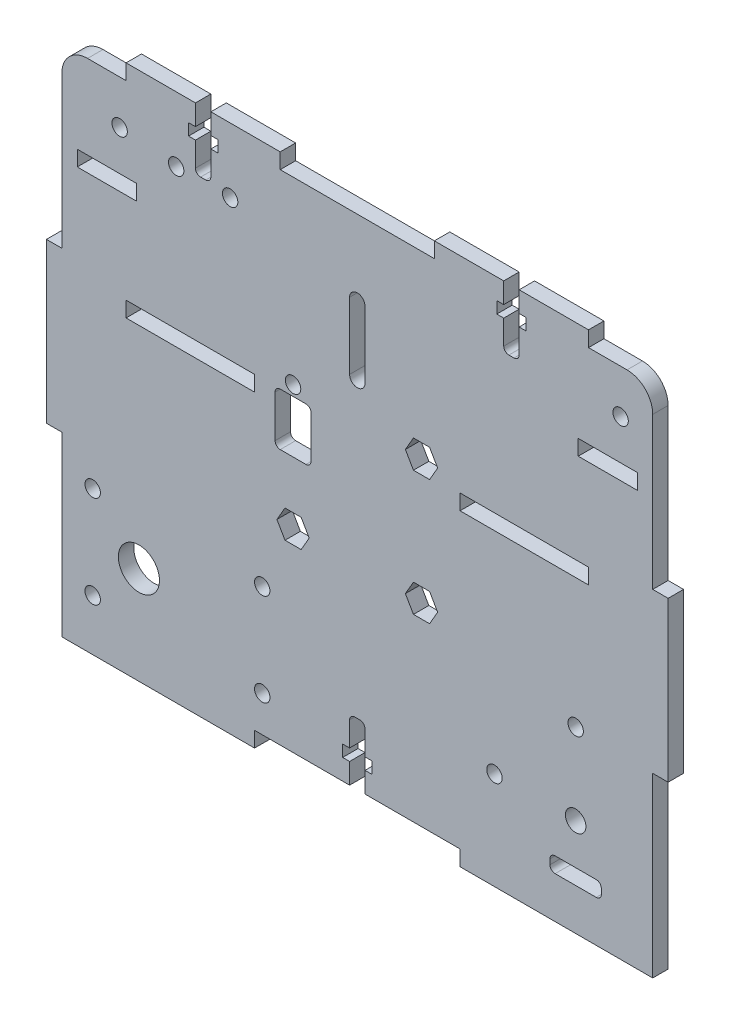
SolidWorks part; units mm, degrees
other "Marcação1"
sketch "Esboço7" plane through (-68, 31.5, 3) normal (-0.6758, 0.2828, 0.6807) x (0.7271, 0.1043, 0.6785)
sketch "Esboço8" plane through (-68, 31.5, 3) normal (-0.6758, 0.2828, 0.6807) x (0.7271, 0.1043, 0.6785)
sketch "Esboço9" plane through (-68, 31.5, 3) normal (-0.6758, 0.2828, 0.6807) x (0.7271, 0.1043, 0.6785)
sketch "Esboço10" plane through (-68, 31.5, 3) normal (-0.6758, 0.2828, 0.6807) x (0.7271, 0.1043, 0.6785)
sketch "Esboço11" plane through (-68, 36.25, 3) normal (-0.6758, 0.2828, 0.6807) x (0.7271, 0.1043, 0.6785)
sketch "Esboço13" plane through (-68, 36.25, 3) normal (-0.6758, 0.2828, 0.6807) x (0.7271, 0.1043, 0.6785)
sketch "Esboço15" plane through (-68, 36.25, 3) normal (-0.6758, 0.2828, 0.6807) x (0.7271, 0.1043, 0.6785)
sketch "Esboço19" plane through (-68, 66.25, 3) normal (-0.6758, 0.2828, 0.6807) x (0.7271, 0.1043, 0.6785)
sketch "Esboço22" plane through (-68, 95.5577, 3) normal (-0.6758, 0.2828, 0.6807) x (0.7271, 0.1043, 0.6785)
sketch "Sketch16" plane through (-60.5, 53, 1.5) normal (-0.6758, 0.2828, 0.6807) x (0.7271, 0.1043, 0.6785)
sketch "Sketch18" plane through (-60.5, 53, 1.5) normal (-0.6758, 0.2828, 0.6807) x (0.7271, 0.1043, 0.6785)
material "Acrylic (Medium-high impact)"
ref_plane "Plano frontal" through (0, 0, 0) normal (0, 0, 1) x (1, 0, 0)
ref_plane "Plano superior" through (0, 0, 0) normal (0, 1, 0) x (1, 0, 0)
ref_plane "Plano direito" through (0, 0, 0) normal (1, 0, 0) x (0, 0, -1)
sketch "Esboço1" plane through (0, 0, 0) normal (0, 0, 1) x (1, 0, 0)
  line L6 (57.5, -50) -> (-57.5, -50)
  line L8 (57.5, -50) -> (57.5, 50)
  line L9 (57.5, 50) -> (-57.5, 50)
  line L10 (-57.5, -50) -> (-57.5, 50)
  line L11 (57.5, -50) -> (-57.5, 50) construction
  line L12 (57.5, 50) -> (-57.5, -50) construction
  point P0 (0, 0)
  dimension "D1" = 100
  dimension "D2" = 115
extrude "Ressalto-extrusão1" add sketch "Esboço1" along normal mid plane 3
sketch "Esboço2" plane through (0, 0, 1.5) normal (0, 0, 1) x (1, 0, 0)
  line L1 (-20, -50) -> (20, -50)
  line L2 (-20, -50) -> (-20, -47)
  line L3 (-20, -47) -> (20, -47)
  line L4 (20, -50) -> (20, -47)
  line L6 (-57.5, -50) -> (57.5, -50) construction
  line L15 (57.5, 50) -> (-57.5, 50) construction
  line L25 (-45, 13) -> (-20, 13)
  line L26 (-45, 13) -> (-45, 10)
  line L29 (-45, 10) -> (-20, 10)
  line L30 (-20, 13) -> (-20, 10)
  line L31 (0, -1.65) -> (0, 1.65) construction
  line L32 (20, 13) -> (20, 10)
  line L33 (45, 10) -> (20, 10)
  line L34 (45, 13) -> (45, 10)
  line L35 (45, 13) -> (20, 13)
  point P6 (0, -47)
  dimension "D4" = 25
  dimension "D3" = 3
  dimension "D1" = 37
  dimension "D2" = 40
  dimension "D5" = 40
extrude "Corte-extrusão1" cut sketch "Esboço2" against normal through all
sketch "Sketch9" plane through (0, 0, 0) normal (0, 0, 1) x (1, 0, 0)
  line L0 (20, -47) -> (-20, -47) construction
  line L1 (-1.5, -47) -> (1.5, -47)
  line L2 (-1.5, -47) -> (-1.5, -43)
  line L3 (-0.5, -35) -> (0.5, -35)
  line L4 (1.5, -47) -> (1.5, -43)
  line L5 (1.5, -40.73) -> (2.85, -40.73)
  line L6 (-2.85, -40.73) -> (-1.5, -40.73)
  line L7 (-2.85, -40.73) -> (-2.85, -43)
  line L8 (-2.85, -43) -> (-1.5, -43)
  line L9 (2.85, -40.73) -> (2.85, -43)
  line L10 (-1.5, -40.73) -> (-1.5, -36)
  line L11 (1.5, -43) -> (2.85, -43)
  line L12 (1.5, -40.73) -> (1.5, -36)
  arc A0 (0.5, -35) -> (1.5, -36) centre (0.5, -36) cw
  arc A1 (-1.5, -36) -> (-0.5, -35) centre (-0.5, -36) cw
  point P6 (0, -35)
  point P18 (1.5, -35)
  point P21 (-1.5, -35)
  dimension "D7" = 1
  dimension "D1" = 3
  dimension "D2" = 12
  dimension "D3" = 2.27
  dimension "D4" = 1.35
  dimension "D5" = 1.35
  dimension "D6" = 4
extrude "Cut-Extrude12" cut sketch "Sketch9" against normal through all both and the other way through all
sketch "Esboço3" plane through (0, 0, 1.5) normal (0, 0, 1) x (1, 0, 0)
  line L0 (57.5, -50) -> (57.5, 50) construction
  line L1 (57.5, 15.5) -> (60.5, 15.5)
  line L2 (57.5, 15.5) -> (57.5, -15.5)
  line L3 (57.5, -15.5) -> (60.5, -15.5)
  line L4 (60.5, 15.5) -> (60.5, -15.5)
  line L5 (0, -1.65) -> (0, 1.65) construction
  line L6 (-57.5, -15.5) -> (-60.5, -15.5)
  line L7 (-57.5, 15.5) -> (-60.5, 15.5)
  line L8 (-57.5, 15.5) -> (-57.5, -15.5)
  line L9 (-60.5, 15.5) -> (-60.5, -15.5)
  line L15 (57.5, 50) -> (-57.5, 50) construction
  line L16 (-45, 50) -> (-15, 50)
  line L17 (-45, 50) -> (-45, 53)
  line L18 (-45, 53) -> (-15, 53)
  line L19 (-15, 50) -> (-15, 53)
  line L20 (15, 50) -> (15, 53)
  line L21 (45, 53) -> (15, 53)
  line L22 (45, 50) -> (45, 53)
  line L23 (45, 50) -> (15, 50)
  line L24 (-57.5, 50) -> (-57.5, -50) construction
  point P6 (57.5, 0)
  dimension "D1" = 3
  dimension "D2" = 31
  dimension "D3" = 30
  dimension "D4" = 15
  dimension "D5" = 12.5
extrude "Ressalto-extrusão2" add sketch "Esboço3" against normal through all
sketch "Esboço30" plane through (0, 0, -1.5) normal (0, 0, -1) x (-1, 0, 0)
  line L2 (57.5, -15.5) -> (57.5, -50) construction
  line L6 (57.5, -50) -> (20, -50) construction
  circle A1 centre (42.5, -31) radius 4
  dimension "D1" = 15
  dimension "D2" = 19
  dimension "D3" = 8
extrude "Corte-extrusão11" cut sketch "Esboço30" against normal through all both and the other way through all
sketch "Esboço4" plane through (0, 0, 1.5) normal (0, 0, 1) x (1, 0, 0)
  line L0 (57.5, -50) -> (57.5, -15.5) construction
  line L76 (-46.5, -31) -> (-38.5, -31) construction
  circle A11 centre (42.5, -31) radius 2
  circle A14 centre (-42.5, -31) radius 4 construction
  dimension "D1" = 15
  dimension "D2" = 4
extrude "Corte-extrusão2" cut sketch "Esboço4" against normal through all
sketch "Esboço31" plane through (0, 0, -1.5) normal (0, 0, -1) x (-1, 0, 0)
  line L1 (57.5, -15.5) -> (57.5, -50) construction
  line L2 (46.5, -31) -> (38.5, -31) construction
  circle A4 centre (51.5, -22) radius 1.5
  circle A5 centre (51.5, -40) radius 1.5
  circle A6 centre (42.5, -31) radius 4 construction
  circle A7 centre (18.5, -22) radius 1.5
  circle A8 centre (18.5, -40) radius 1.5
  dimension "D1" = 3
  dimension "D3" = 6
  dimension "D4" = 18
  dimension "D5" = 33
extrude "Corte-extrusão12" cut sketch "Esboço31" against normal through all both and the other way through all
sketch "Sketch8" [suppressed] plane through (0, 0, -1.5) normal (0, 0, -1) x (-1, 0, 0)
  line L31 (-57.5, 39.6519) -> (-53.4896, 39.6519)
  line L32 (-58, 31.6519) -> (-58, 23.6519) construction
  line L33 (-57.5, 23.6519) -> (-53.4896, 23.6519)
  line L34 (-45, 36.6519) -> (-45, 26.6519)
  line L35 (-57.5, 15.5) -> (-57.5, 50) construction
  line L37 (-48.5, 41.4019) -> (-50, 44)
  line L38 (-50, 44) -> (-53, 44)
  line L39 (-53, 44) -> (-54.5, 41.4019)
  line L40 (-54.5, 41.4019) -> (-53.4896, 39.6519)
  line L42 (-49.5104, 39.6519) -> (-48.5, 41.4019)
  line L43 (-49.5104, 39.6519) -> (-48, 39.6519)
  line L45 (-51.7693, 38.8038) -> (-50.2755, 38.8038) [skipped]
  line L46 (-58, 31.6519) -> (-45, 31.6519) construction
  line L48 (-49.5104, 23.6519) -> (-48.5, 21.9019)
  line L49 (-54.5, 21.9019) -> (-53.4896, 23.6519)
  line L50 (-53, 19.3038) -> (-54.5, 21.9019)
  line L51 (-50, 19.3038) -> (-53, 19.3038)
  line L52 (-48.5, 21.9019) -> (-50, 19.3038)
  line L53 (-49.5104, 23.6519) -> (-48, 23.6519)
  line L54 (-57.5, 23.6519) -> (-57.5, 39.6519)
  line L55 (-58, 39.6519) -> (-57.5, 39.6519) construction
  line L56 (-58, 39.6519) -> (-58, 31.6519) construction
  line L57 (-58, 23.6519) -> (-57.5, 23.6519) construction
  line L58 (-57.5, 50) -> (-45, 50) construction
  line L59 (0, 1.65) -> (0, -1.65) construction
  line L60 (58, 23.6519) -> (57.5, 23.6519) construction
  line L61 (58, 39.6519) -> (58, 31.6519) construction
  line L62 (58, 39.6519) -> (57.5, 39.6519) construction
  line L63 (58, 31.6519) -> (45, 31.6519) construction
  line L64 (58, 31.6519) -> (58, 23.6519) construction
  line L65 (57.5, 23.6519) -> (57.5, 39.6519)
  line L66 (49.5104, 23.6519) -> (48, 23.6519)
  line L67 (48.5, 21.9019) -> (50, 19.3038)
  line L68 (50, 19.3038) -> (53, 19.3038)
  line L69 (53, 19.3038) -> (54.5, 21.9019)
  line L70 (54.5, 21.9019) -> (53.4896, 23.6519)
  line L71 (49.5104, 23.6519) -> (48.5, 21.9019)
  line L72 (49.5104, 39.6519) -> (48, 39.6519)
  line L73 (49.5104, 39.6519) -> (48.5, 41.4019)
  line L74 (54.5, 41.4019) -> (53.4896, 39.6519)
  line L75 (53, 44) -> (54.5, 41.4019)
  line L76 (50, 44) -> (53, 44)
  line L77 (48.5, 41.4019) -> (50, 44)
  line L78 (45, 36.6519) -> (45, 26.6519)
  line L79 (57.5, 23.6519) -> (53.4896, 23.6519)
  line L80 (57.5, 39.6519) -> (53.4896, 39.6519)
  arc A10 (-48, 23.6519) -> (-45, 26.6519) centre (-48, 26.6519) ccw
  arc A12 (-48, 39.6519) -> (-45, 36.6519) centre (-48, 36.6519) cw
  arc A14 (-49.25, 40.1029) -> (-53.75, 40.1029) centre (-51.5, 41.4019) ccw construction
  arc A15 (-49.25, 23.201) -> (-53.75, 23.201) centre (-51.5, 21.9019) cw construction
  arc A16 (49.25, 23.201) -> (53.75, 23.201) centre (51.5, 21.9019) ccw construction
  arc A17 (49.25, 40.1029) -> (53.75, 40.1029) centre (51.5, 41.4019) cw construction
  arc A18 (48, 39.6519) -> (45, 36.6519) centre (48, 36.6519) ccw
  arc A19 (48, 23.6519) -> (45, 26.6519) centre (48, 26.6519) cw
  point P9 (-45, 23.6519)
  point P14 (-45, 39.6519)
  point P17 (-58, 39.6519)
  point P38 (-51.5, 31.6519)
  point P73 (45, 39.6519)
  point P74 (45, 23.6519)
  dimension "D1" = 13
  dimension "D2" = 3
  dimension "D5" = 3
  dimension "D6" = 3
  dimension "D3" = 16
  dimension "D7" = 19.5
  dimension "D8" = 6
sketch "Sketch11" plane through (0, 0, 0) normal (0, 0, 1) x (1, 0, 0)
  line L0 (45, 53) -> (15, 53) construction
  line L1 (28.5, 53) -> (31.5, 53)
  line L2 (28.5, 53) -> (28.5, 49)
  line L3 (29.5, 41) -> (30.5, 41)
  line L4 (31.5, 53) -> (31.5, 49)
  line L5 (15, 53) -> (15, 50) construction
  line L6 (28.5, 46.73) -> (28.5, 42)
  line L7 (27.15, 49) -> (28.5, 49)
  line L8 (27.15, 49) -> (27.15, 46.73)
  line L9 (27.15, 46.73) -> (28.5, 46.73)
  line L10 (32.85, 49) -> (32.85, 46.73)
  line L11 (31.5, 49) -> (32.85, 49)
  line L12 (31.5, 46.73) -> (31.5, 42)
  line L13 (31.5, 46.73) -> (32.85, 46.73)
  line L27 (0, -1.65) -> (0, 1.65) construction
  line L28 (-31.5, 46.73) -> (-32.85, 46.73)
  line L29 (-31.5, 46.73) -> (-31.5, 42)
  line L30 (-31.5, 49) -> (-32.85, 49)
  line L31 (-32.85, 49) -> (-32.85, 46.73)
  line L32 (-27.15, 46.73) -> (-28.5, 46.73)
  line L33 (-27.15, 49) -> (-27.15, 46.73)
  line L34 (-27.15, 49) -> (-28.5, 49)
  line L35 (-28.5, 46.73) -> (-28.5, 42)
  line L36 (-31.5, 53) -> (-31.5, 49)
  line L37 (-29.5, 41) -> (-30.5, 41)
  line L38 (-28.5, 53) -> (-28.5, 49)
  line L39 (-28.5, 53) -> (-31.5, 53)
  arc A0 (30.5, 41) -> (31.5, 42) centre (30.5, 42) ccw
  arc A1 (28.5, 42) -> (29.5, 41) centre (29.5, 42) ccw
  arc A4 (-28.5, 42) -> (-29.5, 41) centre (-29.5, 42) cw
  arc A5 (-30.5, 41) -> (-31.5, 42) centre (-30.5, 42) cw
  point P20 (28.5, 41)
  point P39 (-28.5, 41)
  dimension "D8" = 1
  dimension "D1" = 3
  dimension "D2" = 12
  dimension "D3" = 13.5
  dimension "D4" = 1.35
  dimension "D5" = 2.27
  dimension "D6" = 1.35
  dimension "D7" = 4
extrude "Cut-Extrude14" cut sketch "Sketch11" against normal through all both and the other way through all
sketch "Sketch13" plane through (0, 0, 0) normal (0, 0, 1) x (1, 0, 0)
  line L18 (-10, 13.0193) -> (-15, 13.0193)
  line L19 (-9, 12.0193) -> (-9, 3.8193)
  line L20 (-10, 2.8193) -> (-15, 2.8193)
  line L21 (-16, 12.0193) -> (-16, 3.8193)
  line L23 (15.64, 15.0193) -> (14.07, 17.7386)
  line L24 (14.07, 17.7386) -> (10.93, 17.7386)
  line L25 (10.93, 17.7386) -> (9.36, 15.0193)
  line L26 (9.36, 15.0193) -> (10.93, 12.3)
  line L27 (10.93, 12.3) -> (14.07, 12.3)
  line L28 (14.07, 12.3) -> (15.64, 15.0193)
  line L30 (15.64, -9.2807) -> (14.07, -6.5614)
  line L31 (14.07, -6.5614) -> (10.93, -6.5614)
  line L32 (10.93, -6.5614) -> (9.36, -9.2807)
  line L33 (9.36, -9.2807) -> (10.93, -12)
  line L34 (10.93, -12) -> (14.07, -12)
  line L35 (14.07, -12) -> (15.64, -9.2807)
  line L38 (-9.36, -9.2807) -> (-10.93, -6.5614)
  line L39 (-10.93, -6.5614) -> (-14.07, -6.5614)
  line L40 (-14.07, -6.5614) -> (-15.64, -9.2807)
  line L41 (-15.64, -9.2807) -> (-14.07, -12)
  line L42 (-14.07, -12) -> (-10.93, -12)
  line L43 (-10.93, -12) -> (-9.36, -9.2807)
  line L45 (-12.5, 15.0193) -> (12.5, 15.0193) construction
  circle A1 centre (12.5, 15.0193) radius 1.5 construction
  circle A2 centre (-12.5, -9.2807) radius 1.5 construction
  circle A3 centre (12.5, -9.2807) radius 1.5 construction
  circle A10 centre (-12.5, 15.0193) radius 1.5
  arc A11 (-15, 2.8193) -> (-16, 3.8193) centre (-15, 3.8193) cw
  arc A12 (-9, 3.8193) -> (-10, 2.8193) centre (-10, 3.8193) cw
  arc A13 (-15, 13.0193) -> (-16, 12.0193) centre (-15, 12.0193) ccw
  arc A14 (-10, 13.0193) -> (-9, 12.0193) centre (-10, 12.0193) cw
  circle A15 centre (12.5, 15.0193) radius 2.7193 construction
  circle A16 centre (12.5, -9.2807) radius 2.7193 construction
  circle A17 centre (-12.5, -9.2807) radius 2.7193 construction
  circle A18 centre (-18.5, -22) radius 1.5 construction
  point P10 (0, 15.0193)
  point P16 (-12.5, 13.0193)
  point P19 (-16, 2.8193)
  point P25 (-16, 13.0193)
  dimension "D1" = 3
  dimension "D3" = 25
  dimension "D2" = 24.3
  dimension "D6" = 0.5
  dimension "D4" = 8.5
  dimension "D9" = 1
  dimension "D10" = 3.14
  dimension "D7" = 10.2
  dimension "D8" = 2
extrude "Cut-Extrude16" cut sketch "Sketch13" against normal through all both and the other way through all
sketch "Sketch12" plane through (0, 0, -1.5) normal (0, 0, 1) x (1, 0, 0)
  line L3 (0, 22.2386) -> (0, 35.2386) construction
  line L6 (-1.5, 22.2386) -> (-1.5, 35.2386)
  line L7 (1.5, 22.2386) -> (1.5, 35.2386)
  line L8 (-2, 23.2803) -> (-6, 23.2803)
  line L9 (-2, 22.2386) -> (-6, 22.2386)
  line L10 (-2, 22.2386) -> (-2, 22.7386)
  line L11 (-2, 22.7386) -> (-6, 22.7386)
  line L12 (-6, 22.2386) -> (-6, 22.7386)
  line L13 (-2, 23.2803) -> (-2, 23.7803)
  line L14 (-2, 23.7803) -> (-6, 23.7803)
  line L15 (-6, 23.2803) -> (-6, 23.7803)
  line L16 (-2, 24.322) -> (-6, 24.322)
  line L17 (-2, 24.322) -> (-2, 24.822)
  line L18 (-2, 24.822) -> (-6, 24.822)
  line L19 (-6, 24.322) -> (-6, 24.822)
  line L20 (-2, 25.3636) -> (-6, 25.3636)
  line L21 (-2, 25.3636) -> (-2, 25.8636)
  line L22 (-2, 25.8636) -> (-6, 25.8636)
  line L23 (-6, 25.3636) -> (-6, 25.8636)
  line L24 (-2, 26.4053) -> (-6, 26.4053)
  line L25 (-2, 26.4053) -> (-2, 26.9053)
  line L26 (-2, 26.9053) -> (-6, 26.9053)
  line L27 (-6, 26.4053) -> (-6, 26.9053)
  line L28 (-2, 27.447) -> (-6, 27.447)
  line L29 (-2, 27.447) -> (-2, 27.947)
  line L30 (-2, 27.947) -> (-6, 27.947)
  line L31 (-6, 27.447) -> (-6, 27.947)
  line L32 (-2, 28.4886) -> (-6, 28.4886)
  line L33 (-2, 28.4886) -> (-2, 28.9886)
  line L34 (-2, 28.9886) -> (-6, 28.9886)
  line L35 (-6, 28.4886) -> (-6, 28.9886)
  line L36 (-2, 29.5303) -> (-6, 29.5303)
  line L37 (-2, 29.5303) -> (-2, 30.0303)
  line L38 (-2, 30.0303) -> (-6, 30.0303)
  line L39 (-6, 29.5303) -> (-6, 30.0303)
  line L40 (-2, 30.572) -> (-6, 30.572)
  line L41 (-2, 30.572) -> (-2, 31.072)
  line L42 (-2, 31.072) -> (-6, 31.072)
  line L43 (-6, 30.572) -> (-6, 31.072)
  line L44 (-2, 31.6136) -> (-6, 31.6136)
  line L45 (-2, 31.6136) -> (-2, 32.1136)
  line L46 (-2, 32.1136) -> (-6, 32.1136)
  line L47 (-6, 31.6136) -> (-6, 32.1136)
  line L48 (-2, 32.6553) -> (-6, 32.6553)
  line L49 (-2, 32.6553) -> (-2, 33.1553)
  line L50 (-2, 33.1553) -> (-6, 33.1553)
  line L51 (-6, 32.6553) -> (-6, 33.1553)
  line L52 (-2, 33.697) -> (-6, 33.697)
  line L53 (-2, 33.697) -> (-2, 34.197)
  line L54 (-2, 34.197) -> (-6, 34.197)
  line L55 (-6, 33.697) -> (-6, 34.197)
  line L56 (-2, 34.7386) -> (-6, 34.7386)
  line L57 (-2, 34.7386) -> (-2, 35.2386)
  line L58 (-2, 35.2386) -> (-6, 35.2386)
  line L59 (-6, 34.7386) -> (-6, 35.2386)
  line L66 (14.07, 17.7386) -> (10.93, 17.7386) construction
  circle A1 centre (0, 22.2386) radius 1.5 construction
  arc A4 (-1.5, 22.2386) -> (1.5, 22.2386) centre (0, 22.2386) ccw
  arc A5 (1.5, 35.2386) -> (-1.5, 35.2386) centre (0, 35.2386) ccw
  point P4 (0, 28.7386)
  dimension "D1" = 3
  dimension "D2" = 13
  dimension "D3" = 0.5
  dimension "D4" = 3
  dimension "D5" = 4
  dimension "D6" = 0.5
  dimension "D7" = 13
extrude "Cut-Extrude15" cut sketch "Sketch12" along normal through all contours L7 A5 L6 A4 | A5 L7 A4 L6 region at (0, 28.7386, -1.5)
extrude "Cut-Extrude18" cut sketch "Sketch12<3>" along normal blind 0.1 contours L59 L56 L57 L58 | L55 L52 L53 L54 | L51 L48 L49 L50 | L47 L44 L45 L46 | L39 L36 L37 L38 | L43 L40 L41 L42 | L31 L28 L29 L30 | L35 L32 L33 L34 | L27 L24 L25 L26 | L23 L20 L21 L22 | L19 L16 L17 L18 | L15 L8 L13 L14 | L12 L9 L10 L11 | L56 L59 L58 L57 | L52 L55 L54 L53 | L48 L51 L50 L49 | L44 L47 L46 L45 | L40 L43 L42 L41 | L36 L39 L38 L37 | L32 L35 L34 L33 | L28 L31 L30 L29 | L24 L27 L26 L25 | L20 L23 L22 L21 | L16 L19 L18 L17 | L8 L15 L14 L13 | L9 L12 L11 L10 | L42 L43 L40 L41 | L38 L39 L36 L37 region at (-4, 23.5303, -1.5) region at (-4, 22.4886, -1.5) region at (-4, 24.572, -1.5) region at (-4, 25.6136, -1.5) region at (-4, 26.6553, -1.5) region at (-4, 27.697, -1.5) region at (-4, 28.7386, -1.5) region at (-4, 29.7803, -1.5) region at (-4, 30.822, -1.5) region at (-4, 31.8636, -1.5) region at (-4, 32.9053, -1.5) region at (-4, 33.947, -1.5) region at (-4, 34.9886, -1.5)
sketch "Sketch12<3>" plane through (0, 0, -1.5) normal (0, 0, 1) x (1, 0, 0) same geometry as "Sketch12"
fillet "Fillet1" radius 5 2 edges at (57.5, 50, 0) (-57.5, 50, 0)
sketch "Sketch14" plane through (0, 0, 0) normal (0, 0, 1) x (1, 0, 0)
  line L0 (-30, 42.1706) -> (-30, 58.8294) construction
  line L1 (-45, 53) -> (-15, 53) construction
  line L3 (15, 50) -> (-15, 50) construction
  circle A0 centre (-24.75, 40.4) radius 1.5
  circle A1 centre (-35.25, 40.4) radius 1.5
  point P5 (-30, 53)
  point P7 (-30, 53)
  dimension "D1" = 3
  dimension "D2" = 10.5
  dimension "D3" = 9.6
extrude "Cut-Extrude17" cut sketch "Sketch14" against normal through all both and the other way through all
extrude "Cut-Extrude19" [suppressed] cut sketch "Sketch8" against normal through all both and the other way through all
fillet "Fillet3" [suppressed] radius 1.5
sketch "Sketch15" plane through (0, 0, 0) normal (0, 0, 1) x (1, 0, 0)
  line L0 (57.5, 15.5) -> (57.5, 45) construction
  line L1 (54.5, 33.7) -> (43, 33.7)
  line L2 (54.5, 33.7) -> (54.5, 30.7)
  line L3 (54.5, 30.7) -> (43, 30.7)
  line L4 (43, 33.7) -> (43, 30.7)
  line L5 (52.5, 50) -> (45, 50) construction
  line L6 (0, -1.65) -> (0, 1.65) construction
  line L7 (-43, 33.7) -> (-43, 30.7)
  line L8 (-54.5, 30.7) -> (-43, 30.7)
  line L9 (-54.5, 33.7) -> (-54.5, 30.7)
  line L10 (-54.5, 33.7) -> (-43, 33.7)
  circle A0 centre (51.25, 41.5) radius 1.5
  circle A2 centre (-46.25, 41.5) radius 1.5
  point P8 (48.75, 33.7)
  point P20 (-48.75, 33.7)
  dimension "D4" = 3
  dimension "D7" = 7
  dimension "D8" = 2.5
  dimension "D1" = 11.5
  dimension "D2" = 3
  dimension "D3" = 3
  dimension "D5" = 7.8
  dimension "D6" = 2.5
extrude "Corte GY-53LDK" cut sketch "Sketch15" against normal through all both and the other way through all
sketch "Sketch17" plane through (0, 0, -1.5) normal (0, 0, -1) x (-1, 0, 0)
  line L0 (-42.5, -43) -> (-42.5, -38) construction
  line L4 (-46.5, -38.9087) -> (-38.5, -38.9087)
  line L5 (-47.5, -39.9087) -> (-47.5, -40.9087)
  line L6 (-46.5, -41.9087) -> (-38.5, -41.9087)
  line L7 (-37.5, -39.9087) -> (-37.5, -40.9087)
  line L8 (-33.8397, -38) -> (-51.1603, -38) construction
  circle A0 centre (-42.5, -15.2) radius 1.5
  circle A1 centre (-26.7, -31) radius 1.5
  circle A5 centre (-42.5, -31) radius 12 construction
  arc A6 (-47.5, -40.9087) -> (-46.5, -41.9087) centre (-46.5, -40.9087) ccw
  arc A7 (-46.5, -38.9087) -> (-47.5, -39.9087) centre (-46.5, -39.9087) ccw
  arc A8 (-38.5, -38.9087) -> (-37.5, -39.9087) centre (-38.5, -39.9087) cw
  arc A9 (-38.5, -41.9087) -> (-37.5, -40.9087) centre (-38.5, -40.9087) ccw
  point P16 (-37.3654, -41.3062)
  point P17 (0, 0)
  point P20 (-47.5, -41.9087)
  point P23 (-47.5, -38.9087)
  point P28 (-37.5, -41.9087)
  dimension "D1" = 3
  dimension "D4" = 1
  dimension "D2" = 3
  dimension "D3" = 10
extrude "Cut-Extrude20" cut sketch "Sketch17" against normal through all both and the other way through all
